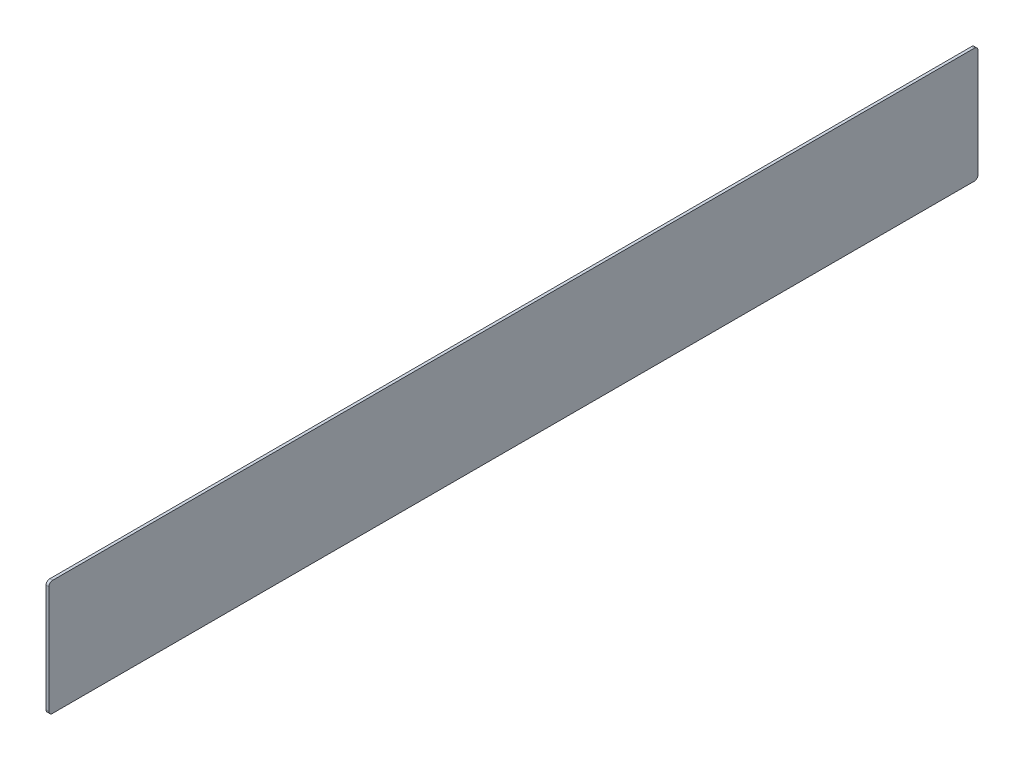
SolidWorks part; units mm, degrees
ref_plane "Front Plane" through (0, 0, 0) normal (0, 0, 1) x (1, 0, 0)
ref_plane "Top Plane" through (0, 0, 0) normal (0, 1, 0) x (1, 0, 0)
ref_plane "Right Plane" through (0, 0, 0) normal (1, 0, 0) x (0, 0, -1)
sketch "Sketch1" plane through (0, 0, 0) normal (1, 0, 0) x (0, 0, -1)
  line L1 (-269.9468, -78.2926) -> (230.0532, -78.2926)
  line L2 (-269.9468, -78.2926) -> (-269.9468, -140.2926)
  line L3 (-269.9468, -140.2926) -> (230.0532, -140.2926)
  line L4 (230.0532, -78.2926) -> (230.0532, -140.2926)
  dimension "D1" = 500
  dimension "D2" = 62
extrude "Boss-Extrude1" add sketch "Sketch1" along normal blind 1.5
fillet "Fillet1" radius 2 4 edges at (0.75, -140.2926, -230.0532) (0.75, -78.2926, -230.0532) (0.75, -140.2926, 269.9468) (0.75, -78.2926, 269.9468)
